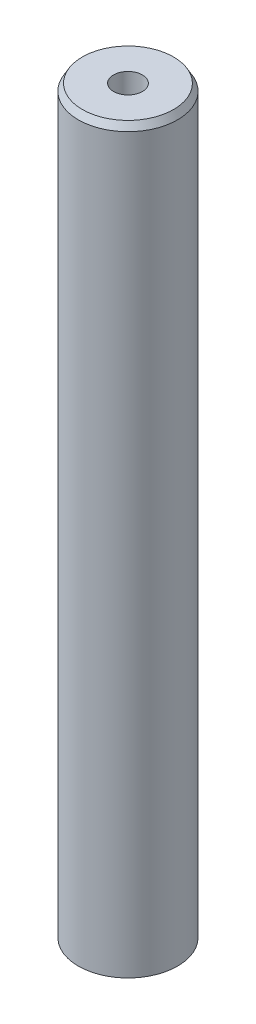
SolidWorks part; units mm, degrees
ref_plane "Front Plane" through (0, 0, 0) normal (0, 0, 1) x (1, 0, 0)
ref_plane "Top Plane" through (0, 0, 0) normal (0, 1, 0) x (1, 0, 0)
ref_plane "Right Plane" through (0, 0, 0) normal (1, 0, 0) x (0, 0, -1)
sketch "Sketch1" plane through (0, 0, 0) normal (0, 1, 0) x (1, 0, 0)
  circle A0 centre (0, 0) radius 40
  dimension "SHAFT_OD" = 80
extrude "Boss-Extrude1" add sketch "Sketch1" along normal blind 600
sketch "Sketch2" plane through (0, 0, 0) normal (0, 1, 0) x (1, 0, 0)
  circle A0 centre (0, 0) radius 11.6442
  dimension "BORE_D" = 23.2884
extrude "Cut-Extrude1" cut sketch "Sketch2" along normal through all
chamfer "Chamfer1" distance 5.5984 angle 30 2 edges at (0, 600, 40) (0, 0, 40) first distance on face at (0, 600, 40) first distance on face at (0, 0, 11.6442)
